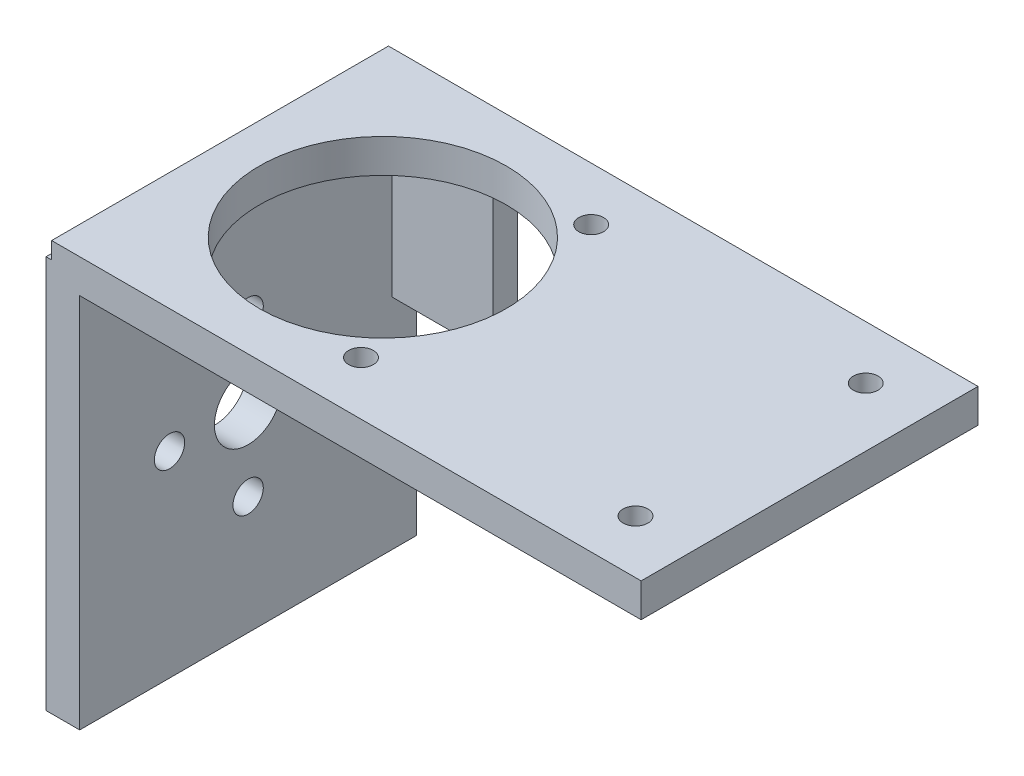
SolidWorks part; units mm, degrees
ref_plane "Front Plane" through (0, 0, 0) normal (0, 0, 1) x (1, 0, 0)
ref_plane "Top Plane" through (0, 0, 0) normal (0, 1, 0) x (1, 0, 0)
ref_plane "Right Plane" through (0, 0, 0) normal (1, 0, 0) x (0, 0, -1)
ref_plane "PZ_m15_000" through (0, 0, -15) normal (0, 0, 1) x (1, 0, 0)
sketch "S_box1" plane through (0, 0, -15) normal (0, 0, 1) x (1, 0, 0)
  line L0 (-15, -17.5) -> (-12, -17.5)
  line L1 (-12, -17.5) -> (-12, 17.5)
  line L2 (-12, 17.5) -> (-15, 17.5)
  line L3 (-15, 17.5) -> (-15, -17.5)
  dimension "P1" = 15
  dimension "P2" = 17.5
  dimension "P3" = 12
  dimension "P4" = 17.5
  dimension "P5" = 12
  dimension "P6" = 17.5
  dimension "P7" = 15
  dimension "P8" = 17.5
extrude "Boss_1" add sketch "S_box1" along normal blind 30
sketch "S_box2" plane through (0, 0, -15) normal (0, 0, 1) x (1, 0, 0)
  line L0 (-14.5, 16) -> (38, 16)
  line L1 (38, 16) -> (38, 19)
  line L2 (38, 19) -> (-14.5, 19)
  line L3 (-14.5, 19) -> (-14.5, 16)
  dimension "P1" = 14.5
  dimension "P2" = 16
  dimension "P3" = 38
  dimension "P4" = 16
  dimension "P5" = 38
  dimension "P6" = 19
  dimension "P7" = 14.5
  dimension "P8" = 19
extrude "Boss_2" add sketch "S_box2" along normal blind 30
sketch "S_box3" plane through (0, 0, -15) normal (0, 0, 1) x (1, 0, 0)
  line L0 (-14.5, 2) -> (-3, 2)
  line L1 (-3, 2) -> (-3, 18.5)
  line L2 (-3, 18.5) -> (-14.5, 18.5)
  line L3 (-14.5, 18.5) -> (-14.5, 2)
  dimension "P1" = 14.5
  dimension "P2" = 2
  dimension "P3" = 3
  dimension "P4" = 2
  dimension "P5" = 3
  dimension "P6" = 18.5
  dimension "P7" = 14.5
  dimension "P8" = 18.5
extrude "Boss_3" add sketch "S_box3" along normal blind 2.2
ref_plane "PX_m15_100" through (-15.1, 0, 0) normal (1, 0, 0) x (0, 0, -1)
sketch "S_hole4" plane through (-15.1, 0, 0) normal (1, 0, 0) x (0, 0, -1)
  circle A0 centre (0, 0) radius 3
  dimension "D1_S_hole4" = 6
extrude "Hole_4" cut sketch "S_hole4" along normal blind 3.2
sketch "S_hole5" plane through (-15.1, 0, 0) normal (1, 0, 0) x (0, 0, -1)
  circle A0 centre (0, -7) radius 1.35
  dimension "D1_S_hole5" = 2.7
  dimension "P2" = 7
extrude "Hole_5" cut sketch "S_hole5" along normal blind 3.2
sketch "S_hole6" plane through (-15.1, 0, 0) normal (1, 0, 0) x (0, 0, -1)
  circle A0 centre (-7, 0) radius 1.35
  dimension "D1_S_hole6" = 2.7
  dimension "P2" = 7
extrude "Hole_6" cut sketch "S_hole6" along normal blind 3.2
sketch "S_hole7" plane through (-15.1, 0, 0) normal (1, 0, 0) x (0, 0, -1)
  circle A0 centre (0, 7) radius 1.35
  dimension "D1_S_hole7" = 2.7
  dimension "P2" = 7
extrude "Hole_7" cut sketch "S_hole7" along normal blind 3.2
sketch "S_hole8" plane through (-15.1, 0, 0) normal (1, 0, 0) x (0, 0, -1)
  circle A0 centre (7, 0) radius 1.35
  dimension "D1_S_hole8" = 2.7
  dimension "P2" = 7
extrude "Hole_8" cut sketch "S_hole8" along normal blind 3.2
ref_plane "PY_p15_900" through (0, 15.9, 0) normal (0, 1, 0) x (1, 0, 0)
sketch "S_hole9" plane through (0, 15.9, 0) normal (0, 1, 0) x (1, 0, 0)
  circle A0 centre (0, 0) radius 11
  dimension "D1_S_hole9" = 22
extrude "Hole_9" cut sketch "S_hole9" along normal blind 3.2
sketch "S_hole10" plane through (0, 15.9, 0) normal (0, 1, 0) x (1, 0, 0)
  circle A0 centre (8.3, 10.25) radius 1.1
  dimension "D1_S_hole10" = 2.2
  dimension "P2" = 8.3
  dimension "P3" = 10.25
extrude "Hole_10" cut sketch "S_hole10" along normal blind 3.2
sketch "S_hole11" plane through (0, 15.9, 0) normal (0, 1, 0) x (1, 0, 0)
  circle A0 centre (8.3, -10.25) radius 1.1
  dimension "D1_S_hole11" = 2.2
  dimension "P2" = 8.3
  dimension "P3" = 10.25
extrude "Hole_11" cut sketch "S_hole11" along normal blind 3.2
sketch "S_hole12" plane through (0, 15.9, 0) normal (0, 1, 0) x (1, 0, 0)
  circle A0 centre (32.75, 10.25) radius 1.1
  dimension "D1_S_hole12" = 2.2
  dimension "P2" = 32.75
  dimension "P3" = 10.25
extrude "Hole_12" cut sketch "S_hole12" along normal blind 3.2
sketch "S_hole13" plane through (0, 15.9, 0) normal (0, 1, 0) x (1, 0, 0)
  circle A0 centre (32.75, -10.25) radius 1.1
  dimension "D1_S_hole13" = 2.2
  dimension "P2" = 32.75
  dimension "P3" = 10.25
extrude "Hole_13" cut sketch "S_hole13" along normal blind 3.2
equation "\"plate_t\" = 3"
equation "\"clearance\" = 0.4"
